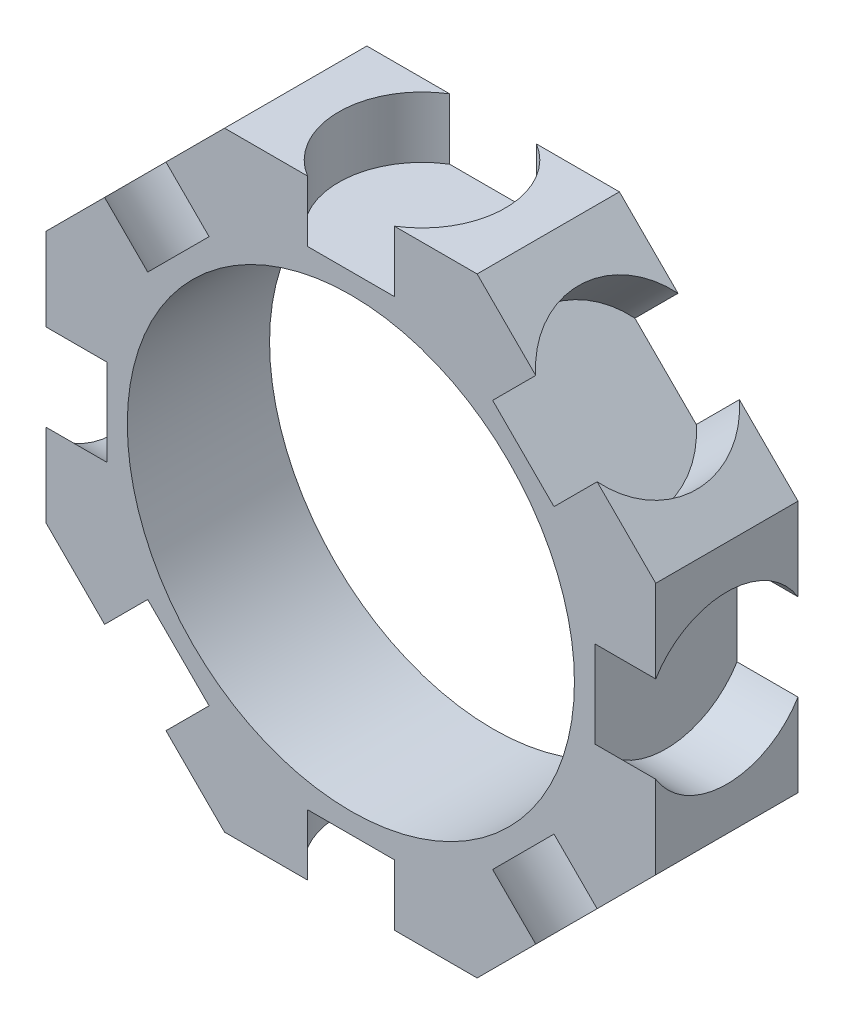
SolidWorks part; units mm, degrees
ref_plane "Top Plane" through (0, 0, 0) normal (0, 0, 1) x (1, 0, 0)
ref_plane "Right Plane" through (0, 0, 0) normal (0, 1, 0) x (1, 0, 0)
ref_plane "Front Plane" through (0, 0, 0) normal (1, 0, 0) x (0, 0, -1)
ref_axis "x-axis" through (-88.99, 0, 0) along (1, 0, 0)
ref_axis "y-axis" through (0, -55, 0) along (0, 1, 0)
ref_axis "z-axis" through (0, 0, 55) along (0, 0, -1)
sketch "Sketch1" plane through (0, 0, 0) normal (0, 0, 1) x (1, 0, 0)
  line L0 (6.2132, 15) -> (-6.2132, 15)
  line L1 (-15, 6.2132) -> (-15, -6.2132)
  line L2 (-15, -6.2132) -> (-6.2132, -15)
  line L3 (-6.2132, -15) -> (6.2132, -15)
  line L4 (6.2132, -15) -> (15, -6.2132)
  line L5 (15, -6.2132) -> (15, 6.2132)
  line L6 (15, 6.2132) -> (6.2132, 15)
  line L7 (-6.2132, 15) -> (-15, 6.2132)
  line L8 (-15, 0) -> (0, 0) construction
  circle A0 centre (0, 0) radius 11
  circle A1 centre (0, 0) radius 15 construction
  dimension "D1" = 22
  dimension "D2" = 15
extrude "Boss-Extrude1" add sketch "Sketch1" along normal mid plane 7
sketch "Sketch2" plane through (0, -15, 0) normal (0, -1, 0) x (-1, 0, 0)
  circle A0 centre (0, 0) radius 4.1
  dimension "D1" = 8.2
extrude "Cut-Extrude3" cut sketch "Sketch2" against normal blind 3
pattern_circular "CirPattern1" count 8 over 360 about axis through (0, 0, 3.5) along (0, 0, 1) of "Cut-Extrude3"
